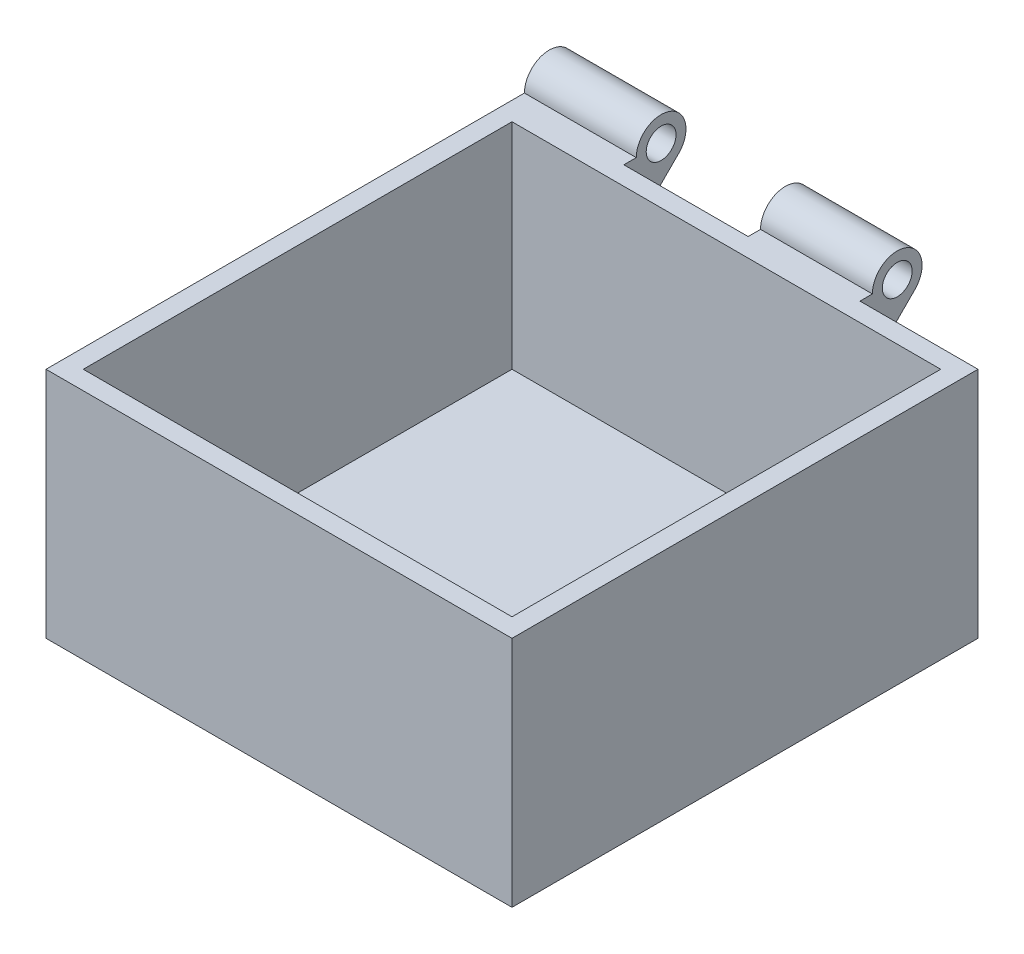
SolidWorks part; units mm, degrees
ref_plane "Front Plane" through (0, 0, 0) normal (0, 0, 1) x (1, 0, 0)
ref_plane "Top Plane" through (0, 0, 0) normal (0, 1, 0) x (1, 0, 0)
ref_plane "Right Plane" through (0, 0, 0) normal (1, 0, 0) x (0, 0, -1)
sketch "Sketch1" plane through (0, 0, 0) normal (0, 1, 0) x (1, 0, 0)
  line L1 (-47.625, 47.625) -> (47.625, 47.625)
  line L2 (-47.625, 47.625) -> (-47.625, -47.625)
  line L3 (-47.625, -47.625) -> (47.625, -47.625)
  line L4 (47.625, 47.625) -> (47.625, -47.625)
  point P4 (0, 47.625)
  point P6 (47.625, 0)
  dimension "D1" = 95.25
  dimension "D2" = 95.25
extrude "Boss-Extrude1" add sketch "Sketch1" along normal blind 47.625
shell "Shell1" thickness 3.81 removed face at (0, 47.625, 0)
sketch "Sketch2" plane through (-47.625, 0, 0) normal (-1, 0, 0) x (0, 0, 1)
  line L0 (-58.8371, 44.0329) -> (-47.625, 32.8208)
  line L1 (-47.625, 47.625) -> (-47.625, 0) construction
  line L2 (-47.625, 47.625) -> (-50.165, 47.625)
  arc A0 (-50.165, 47.625) -> (-58.8371, 44.0329) centre (-55.245, 47.625) ccw
  circle A1 centre (-55.245, 47.625) radius 3.048
  line M5 (-47.625, 47.625) -> (-47.625, 0)
  dimension "D1" = 7.62
  dimension "D2" = 45
  dimension "D3" = 10.16
  dimension "D4" = 6.096
extrude "Boss-Extrude2" add sketch "Sketch2" against normal blind 22.86 contours L2 A0 L0 A1 M5 region at (-47.625, 43.8107, -52.624)
sketch "Sketch5" plane through (47.625, 0, 0) normal (1, 0, 0) x (0, 0, -1)
  line L3 (50.165, 47.625) -> (47.625, 47.625)
  line L4 (47.625, 47.625) -> (47.625, 32.8208)
  line L5 (47.625, 32.8208) -> (58.8371, 44.0329)
  line L6 (50.165, 47.625) -> (47.625, 47.625)
  line L7 (47.625, 47.625) -> (47.625, 32.8208)
  line L8 (47.625, 32.8208) -> (58.8371, 44.0329)
  circle A1 centre (55.245, 47.625) radius 3.048
  circle A2 centre (55.245, 47.625) radius 3.048
  arc A3 (58.8371, 44.0329) -> (50.165, 47.625) centre (55.245, 47.625) ccw
  arc A4 (58.8371, 44.0329) -> (50.165, 47.625) centre (55.245, 47.625) ccw
  dimension "D1" = 0
  dimension "D2" = 0
extrude "Boss-Extrude3" add sketch "Sketch5" against normal blind 22.86 from offset 24.13 offset against normal yes
